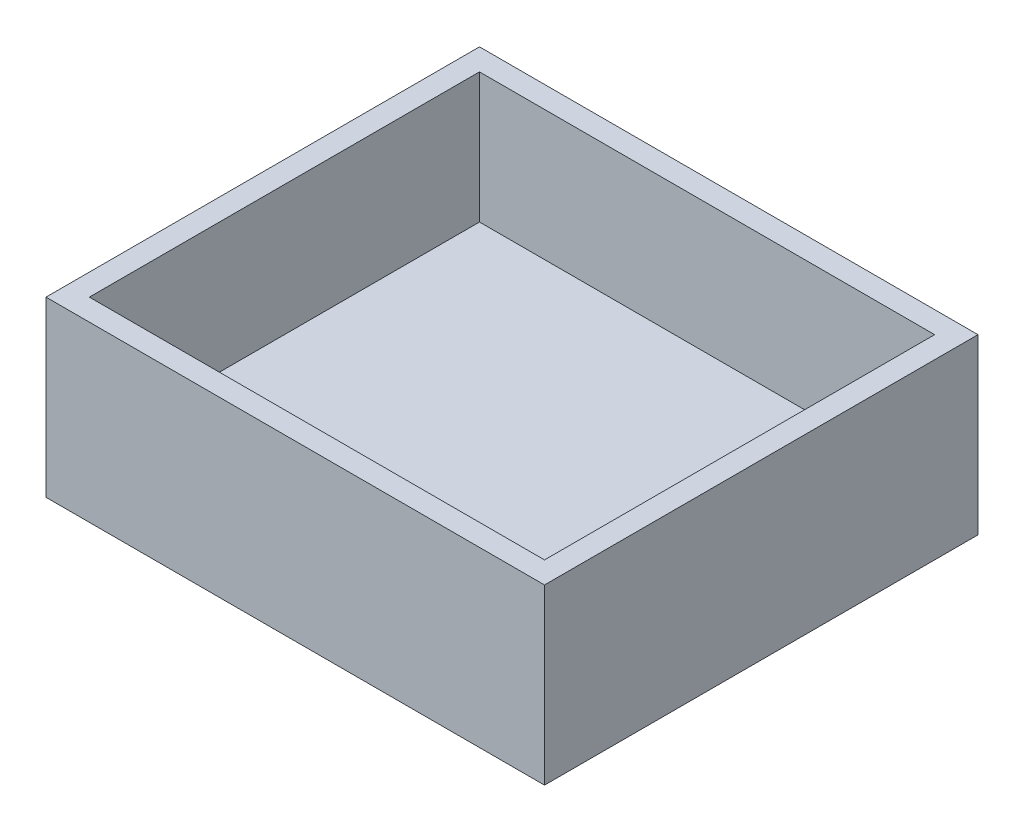
SolidWorks part; units mm, degrees
ref_plane "Front Plane" through (0, 0, 0) normal (0, 0, 1) x (1, 0, 0)
ref_plane "Top Plane" through (0, 0, 0) normal (0, 1, 0) x (1, 0, 0)
ref_plane "Right Plane" through (0, 0, 0) normal (1, 0, 0) x (0, 0, -1)
sketch "Sketch2" plane through (0, 0, 0) normal (0, 1, 0) x (1, 0, 0)
  line L0 (0, 20.2453) -> (0, -25.1679) construction
  line L1 (0, 0) -> (11.5, 0)
  line L2 (11.5, 0) -> (11.5, 10)
  line L3 (11.5, 10) -> (0, 10)
  line L4 (0, 10) -> (0, 0)
  line L5 (5.75, 10) -> (5.75, 0) construction
  line L6 (0, 5) -> (11.5, 5) construction
  line L8 (0.5, 0.5) -> (11, 0.5)
  line L9 (0.5, 0.5) -> (0.5, 9.5)
  line L10 (0.5, 9.5) -> (11, 9.5)
  line L11 (11, 0.5) -> (11, 9.5)
  line L12 (0.5, 0.5) -> (11, 9.5) construction
  line L13 (0.5, 9.5) -> (11, 0.5) construction
  point P11 (5.75, 5)
  dimension "D1" = 11.5
  dimension "D2" = 10
  dimension "D3" = 9
  dimension "D4" = 10.5
extrude "Boss-Extrude2" add sketch "Sketch2" along normal blind 1 contours L8 L11 L10 L9 region at (5.75, 0, -5)
extrude "Boss-Extrude3" add sketch "Sketch2<3>" along normal blind 4
sketch "Sketch2<3>" plane through (0, 0, 0) normal (0, 1, 0) x (1, 0, 0) same geometry as "Sketch2"
